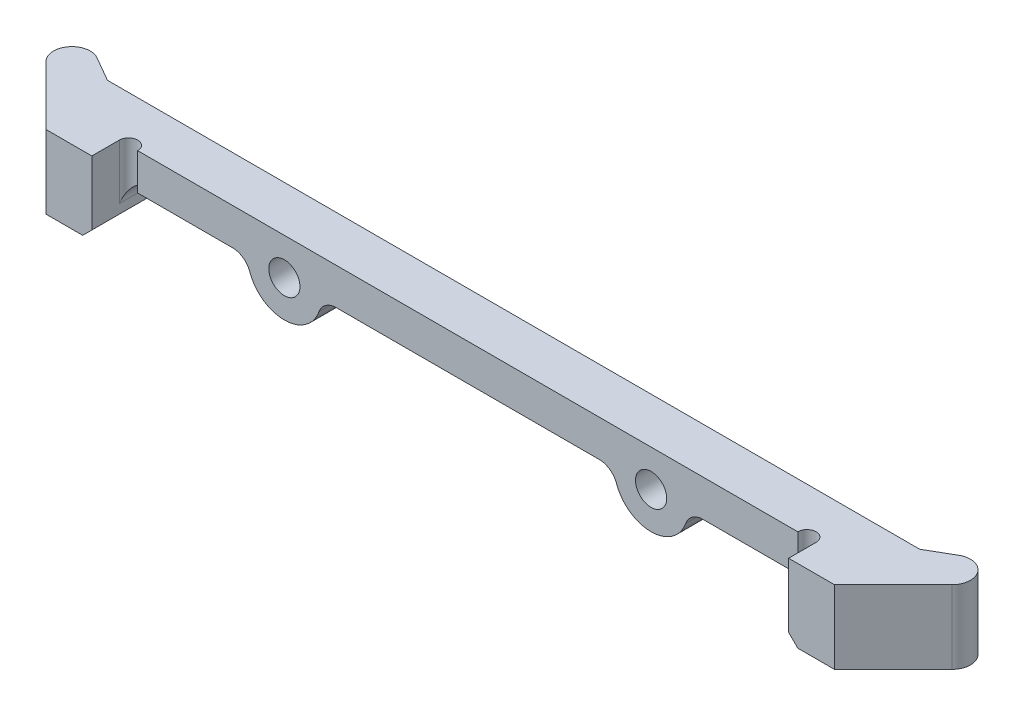
SolidWorks part; units mm, degrees
material "A2017"
ref_plane "正面" through (0, 0, 0) normal (0, 0, 1) x (1, 0, 0)
ref_plane "平面" through (0, 0, 0) normal (0, 1, 0) x (1, 0, 0)
ref_plane "右側面" through (0, 0, 0) normal (1, 0, 0) x (0, 0, -1)
sketch "ｽｹｯﾁ1" plane through (0, 0, 0) normal (0, 1, 0) x (1, 0, 0)
  line L0 (0, 0) -> (0, 22.3684) construction
  line L1 (-38, 0) -> (38, 0)
  line L2 (38, 0) -> (38, -3)
  line L3 (38, -3) -> (43, -3)
  line L4 (-38, -3) -> (-43, -3)
  line L5 (-38, 0) -> (-38, -3)
  line L6 (43, -3) -> (49.4142, 3.4142)
  line L7 (-43, -3) -> (-49.4142, 3.4142)
  line L8 (-44.2972, 5) -> (44.2972, 5)
  line L9 (47, 6.5605) -> (44.2972, 5)
  line L10 (50, 8.3293) -> (50, -3) construction
  line L11 (-50, 8.3293) -> (-50, -3) construction
  line L12 (-47, 6.5605) -> (-44.2972, 5)
  line L13 (-43, -3) -> (-49.4142, 3.4142)
  arc A0 (49.4142, 3.4142) -> (47, 6.5605) centre (48, 4.8284) ccw
  arc A1 (-49.4142, 3.4142) -> (-47, 6.5605) centre (-48, 4.8284) cw
  point P14 (0, 5)
  dimension "D8" = 2
  dimension "D1" = 5
  dimension "D2" = 3
  dimension "D3" = 76
  dimension "D4" = 45
  dimension "D5" = 30
  dimension "D6" = 5
  dimension "D7" = 100
extrude "ﾎﾞｽ - 押し出し1" add sketch "ｽｹｯﾁ1" along normal mid plane 8 contours A1 L7 L4 L5 L1 L2 L3 L6 A0 L9 L8 L12 region at (0, 0, -2.3316)
sketch "ｽｹｯﾁ2" plane through (0, 4, 0) normal (0, 1, 0) x (1, 0, 0)
  line L0 (-38, 0) -> (38, 0) construction
  circle A0 centre (-37, 0) radius 1
  circle A1 centre (37, 0) radius 1
  dimension "D1" = 2
extrude "ｶｯﾄ - 押し出し1" cut sketch "ｽｹｯﾁ2" against normal up to surface (8 mm away) up to face at (0, -4, -1.6722)
hole_wizard "M3 すきま穴1" positions "ｽｹｯﾁ3" profile "ｽｹｯﾁ4" hole size "M3" standard "JIS" end condition through all
sketch "ｽｹｯﾁ3" plane through (0, 0, 0) normal (0, 0, 1) x (1, 0, 0)
  point P0 (20, 0)
  point P3 (-20, 0)
sketch "ｽｹｯﾁ4" plane through (20, 0, 0) normal (1, 0, 0) x (0, -1, 0)
  line L0 (0, 0) -> (0, 6.8284)
  line L1 (0, 6.8284) -> (1.7, 6.8284)
  line L2 (1.7, 6.8284) -> (1.7, 0)
  line L5 (1.7, 0) -> (0, 0)
  line L11 (0, -6.35) -> (0, 107.95) construction
  dimension "通し穴の直径" = 3.4
  dimension "通し穴の深さ" = 6.8284
sketch "ｽｹｯﾁ5" plane through (0, 0, 0) normal (0, 0, 1) x (1, 0, 0)
  line L0 (-36, 4) -> (36, 4) construction
  line L2 (-38, -4) -> (38, -4)
  line L3 (-38, -4) -> (-38, 0)
  line L4 (-38, 0) -> (38, 0)
  line L5 (38, -4) -> (38, 0)
  line L6 (38, 4) -> (38, -4) construction
  circle A0 centre (-20, 0) radius 4
  circle A1 centre (20, 0) radius 4
  line M3 (-36, -4) -> (36, -4)
  line M4 (36, -4) -> (36, 4)
  line M6 (-36, 4) -> (-36, -4)
extrude "ｶｯﾄ - 押し出し2" cut sketch "ｽｹｯﾁ5" against normal through all contours A0 L4 M6 M3 | A1 L4 A0 L2 | A1 L4 M3 M4 | L2 L5 L4 M4 | L4 L3 L2 M6 region at (-37, -2, 0) region at (-29.5398, -2.0739, 0) region at (0, -2.0563, 0) region at (29.5398, -2.0739, 0) region at (37, -2, 0)
fillet "ﾌｨﾚｯﾄ1" radius 2 6 edges at (38, 0, -2.5) (24, 0, -2.5) (16, 0, -2.5) (-16, 0, -2.5) (-24, 0, -2.5) (-38, 0, -2.5)
chamfer "面取り1" distance 1 angle 45 2 edges at (-38, -4, -1) (38, -4, -1)
sketch "ｽｹｯﾁ6" plane through (0, 0, 0) normal (1, 0, 0) x (0, 0, -1)
  line L1 (5, 4) -> (13, 4)
  line L2 (5, 4) -> (5, -4)
  line L3 (5, -4) -> (13, -4)
  line L4 (13, 4) -> (13, -4)
  dimension "D1" = 8
extrude "ﾎﾞｽ - 押し出し2" [suppressed] add sketch "ｽｹｯﾁ6" along normal mid plane 10
fillet "ﾌｨﾚｯﾄ2" [suppressed] radius 3
sketch "ｽｹｯﾁ8" [suppressed] plane through (0, -4, 0) normal (0, -1, 0) x (1, 0, 0)
  line L0 (5, -5) -> (-5, -5) construction
  circle A0 centre (0, -5) radius 5
extrude "ﾎﾞｽ - 押し出し3" [suppressed] add sketch "ｽｹｯﾁ8" against normal up to surface (4 mm away) up to face at (0, 0, -2.5)
sketch "ｽｹｯﾁ7" [suppressed] plane through (0, -4, 0) normal (0, -1, 0) x (1, 0, 0)
  line L0 (0, -13) -> (0, -7) construction
  line L1 (5, -13) -> (-5, -13) construction
  line L2 (-3, -13) -> (-3, -7)
  line L3 (3, -13) -> (3, -7)
  arc A0 (-3, -13) -> (3, -13) centre (0, -13) ccw
  arc A1 (3, -7) -> (-3, -7) centre (0, -7) ccw
  point P5 (0, -10)
  dimension "D1" = 6
  dimension "D2" = 6
extrude "ｶｯﾄ - 押し出し3" [suppressed] cut sketch "ｽｹｯﾁ7" against normal up to surface (8 mm away) up to face at (0, 4, -1.5762)
sketch "ｽｹｯﾁ9" [suppressed] plane through (0, -4, 0) normal (0, -1, 0) x (1, 0, 0)
  line L0 (-5, -5) -> (-5, -13) construction
  line L1 (-5, -7) -> (5, -7)
  line L2 (-5, -7) -> (-5, -11)
  line L3 (-5, -11) -> (5, -11)
  line L4 (5, -7) -> (5, -11)
  line L5 (5, -5) -> (5, -13) construction
  dimension "D1" = 4
extrude "ｶｯﾄ - 押し出し4" [suppressed] cut sketch "ｽｹｯﾁ9" against normal blind 6
sketch "ｽｹｯﾁ10" [suppressed] plane through (0, 0, 0) normal (0, -1, 0) x (1, 0, 0)
  line L0 (-5, -8) -> (-5, -11) construction
  line L1 (-5, -7) -> (-5.1716, -7)
  line L2 (-5, -7) -> (-5, -8)
  line L3 (-5, -8) -> (-5.1716, -8)
  line L4 (-5.1716, -7) -> (-5.1716, -8)
  line L5 (0, 0) -> (0, -13.0364) construction
  line L6 (5.1716, -7) -> (5.1716, -8)
  line L7 (5, -8) -> (5.1716, -8)
  line L8 (5, -7) -> (5, -8)
  line L9 (5, -7) -> (5.1716, -7)
  arc A0 (-5, -8) -> (-8, -5) centre (-8, -8) ccw construction
extrude "ｶｯﾄ - 押し出し5" [suppressed] cut sketch "ｽｹｯﾁ10" against normal up to surface (2 mm away) up to face at (-43.8485, -4, -2.5055)
